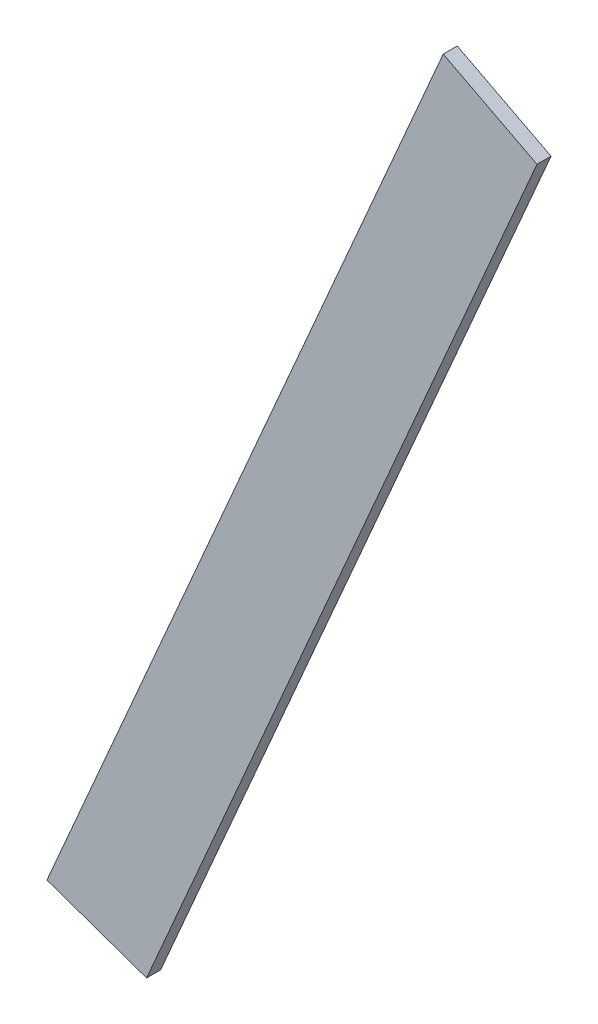
SolidWorks part; units mm, degrees
ref_plane "Front Plane" through (0, 0, 0) normal (0, 0, 1) x (1, 0, 0)
ref_plane "Top Plane" through (0, 0, 0) normal (0, 1, 0) x (1, 0, 0)
ref_plane "Right Plane" through (0, 0, 0) normal (1, 0, 0) x (0, 0, -1)
sketch "Sketch1" plane through (0, 0, 0) normal (0, 0, 1) x (1, 0, 0)
  line L0 (31.6183, -12.2543) -> (17.4323, -7.2643)
  line L2 (17.4323, -7.2643) -> (73.8509, 122.7737)
  line L4 (31.6183, -12.2543) -> (87.2019, 115.8592)
  line L5 (87.2019, 115.8592) -> (73.8509, 122.7737)
  line L6 (147.8865, 84.4306) -> (-29.7093, 176.4076) construction
  line L7 (-92.41, 31.3735) -> (96.2581, -34.9918) construction
  dimension "D1" = 15
extrude "Boss-Extrude1" add sketch "Sketch1" along normal blind 2
ref_plane "Plane1" through (24.2035, -10.501, 0) normal (0.9174, -0.398, 0) x (0, 0, -1)
